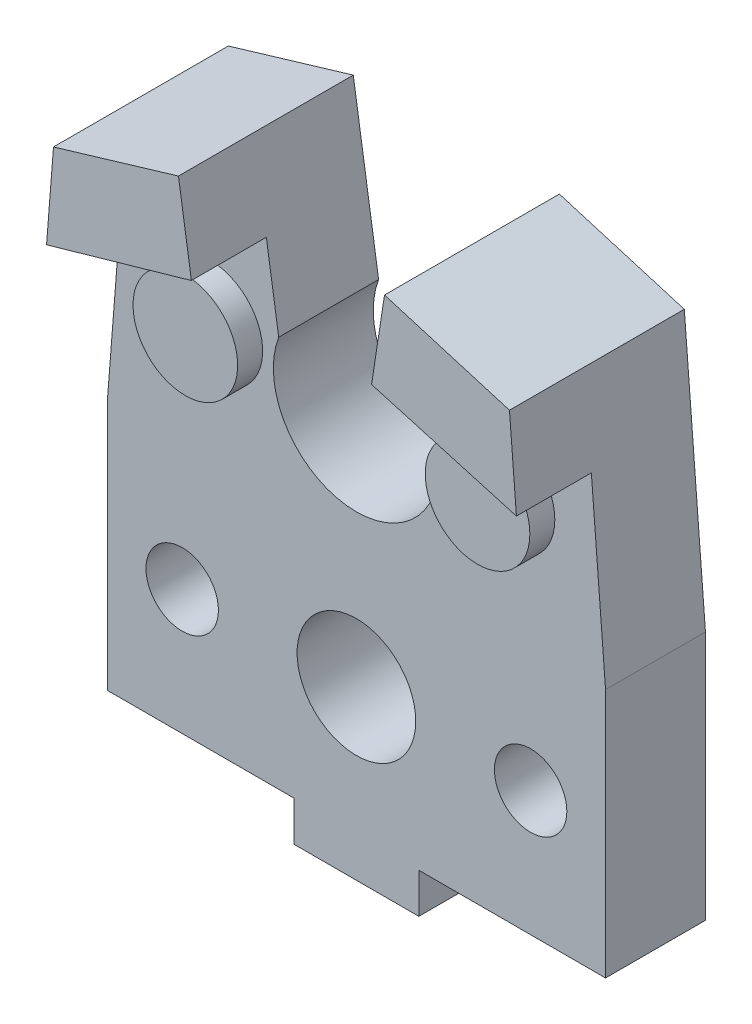
SolidWorks part; units mm, degrees
material "ABS"
ref_plane "Front Plane" through (0, 0, 0) normal (0, 0, 1) x (1, 0, 0)
ref_plane "Top Plane" through (0, 0, 0) normal (0, 1, 0) x (1, 0, 0)
ref_plane "Right Plane" through (0, 0, 0) normal (1, 0, 0) x (0, 0, -1)
sketch "Sketch1" plane through (0, 0, 0) normal (0, 0, 1) x (1, 0, 0)
  line L0 (0, 0) -> (0, 31.5935) construction
  line L1 (-9.975, 0) -> (9.975, 0)
  line L2 (-9.975, 0) -> (-9.975, 10)
  line L3 (9.975, 10) -> (9.1281, 20.764)
  line L4 (9.975, 0) -> (9.975, 10)
  line L5 (9.1281, 20.764) -> (4.1251, 22.2565)
  line L6 (4.1251, 22.2565) -> (3.1105, 15.675)
  line L7 (-4.1251, 22.2565) -> (-3.1105, 15.675)
  line L8 (-9.1281, 20.764) -> (-4.1251, 22.2565)
  line L9 (-9.975, 10) -> (-9.1281, 20.764)
  arc A0 (-3.1105, 15.675) -> (3.1105, 15.675) centre (0, 14.5) ccw
  point P5 (0, 11.175)
  dimension "D3" = 3.325
  dimension "D1" = 19.95
  dimension "D2" = 10
extrude "Boss-Extrude1" add sketch "Sketch1" along normal blind 4 contours L2 L9 L8 L7 A0 L6 L5 L3 L4 L1
sketch "Sketch2" plane through (0, 0, 0) normal (0, 0, -1) x (-1, 0, 0)
  line L0 (9.975, 0) -> (-9.975, 0) construction
  line L1 (-2.5, 0) -> (2.5, 0)
  line L2 (-2.5, 0) -> (-2.5, -1.6)
  line L3 (-2.5, -1.6) -> (2.5, -1.6)
  line L4 (2.5, 0) -> (2.5, -1.6)
  point P6 (0, 0)
  dimension "D1" = 5
  dimension "D2" = 1.6
extrude "Boss-Extrude2" add sketch "Sketch2" against normal up to vertex (4 mm away) up to point (-9.975, 0, 4)
sketch "Sketch3" plane through (0, 0, 0) normal (0, 1, 0) x (1, 0, 0)
  line L0 (0, 0) -> (0, -4) construction
  line L1 (2.5, -4) -> (-2.5, -4) construction
  circle A0 centre (0, -2) radius 2.25
  dimension "D1" = 4.5
extrude "Cut-Extrude1" [suppressed] cut sketch "Sketch3" against normal through all and the other way through all
sketch "Sketch4" [suppressed] plane through (0, 0, 0) normal (0, 1, 0) x (1, 0, 0)
  circle A0 centre (0, -4) radius 3.8
  circle A1 centre (0, -4) radius 2.25 construction
  dimension "D1" = 7.6
extrude "Cut-Extrude2" [suppressed] cut sketch "Sketch4" along normal through all and the other way blind 1.3316 from offset 5
sketch "Sketch5" plane through (0, 0, 4) normal (0, 0, 1) x (1, 0, 0)
  line L0 (6.975, 5) -> (9.975, 5) construction
  line L1 (9.975, 0) -> (9.975, 10) construction
  circle A0 centre (6.975, 5) radius 1.45
  dimension "D1" = 2.9
  dimension "D2" = 3
extrude "Cut-Extrude3" cut sketch "Sketch5" against normal blind 14.2
sketch "Sketch6" plane through (0, 0, 4) normal (0, 0, 1) x (1, 0, 0)
  line L0 (9.975, 0) -> (9.975, 10) construction
  line L1 (6.975, 8) -> (9.975, 8)
  line L3 (6.975, 2) -> (9.975, 2)
  line L4 (9.975, 8) -> (9.975, 2)
  arc A0 (6.975, 8) -> (6.975, 2) centre (6.975, 5) ccw
  circle A1 centre (6.975, 5) radius 1.45 construction
  dimension "D1" = 6
extrude "Cut-Extrude5" [suppressed] cut sketch "Sketch6" against normal blind 2
mirror "Mirror1" about plane through (0, 0, 0) normal (1, 0, 0) of "Cut-Extrude5", "Cut-Extrude3"
sketch "Sketch7" plane through (0, 0, 4) normal (0, 0, 1) x (1, 0, 0)
  line L0 (0, -1.6) -> (0, 5.1) construction
  line L1 (2.5, -1.6) -> (-2.5, -1.6) construction
  circle A0 centre (0, 5.1) radius 2.375
  dimension "D1" = 4.75
  dimension "D2" = 6.7
extrude "Cut-Extrude6" cut sketch "Sketch7" against normal blind 15 contours A0
sketch "Sketch8" plane through (0, 0, 4) normal (0, 0, 1) x (1, 0, 0)
  line L0 (0, 0) -> (0, 20.4736) construction
  circle A0 centre (5.8496, 14.8759) radius 2.0945
  circle A1 centre (-5.8496, 14.8759) radius 2.0945
extrude "Boss-Extrude3" add sketch "Sketch8" along normal blind 1
sketch "Sketch9" plane through (0, 0, 4) normal (0, 0, 1) x (1, 0, 0)
  line L0 (4.1251, 22.2565) -> (3.6067, 18.8935)
  line L1 (4.1251, 22.2565) -> (3.1105, 15.675) construction
  line L2 (3.6067, 18.8935) -> (9.406, 17.2313)
  line L3 (9.975, 10) -> (9.1281, 20.764) construction
  line L4 (9.406, 17.2313) -> (9.1281, 20.764)
  line L5 (9.1281, 20.764) -> (4.1251, 22.2565)
  line L6 (0, 14.5) -> (0, 21.6581) construction
  line L7 (-9.1281, 20.764) -> (-4.1251, 22.2565)
  line L8 (-9.406, 17.2313) -> (-9.1281, 20.764)
  line L9 (-3.6067, 18.8935) -> (-9.406, 17.2313)
  line L10 (-4.1251, 22.2565) -> (-3.6067, 18.8935)
extrude "Boss-Extrude4" add sketch "Sketch9" along normal blind 3
